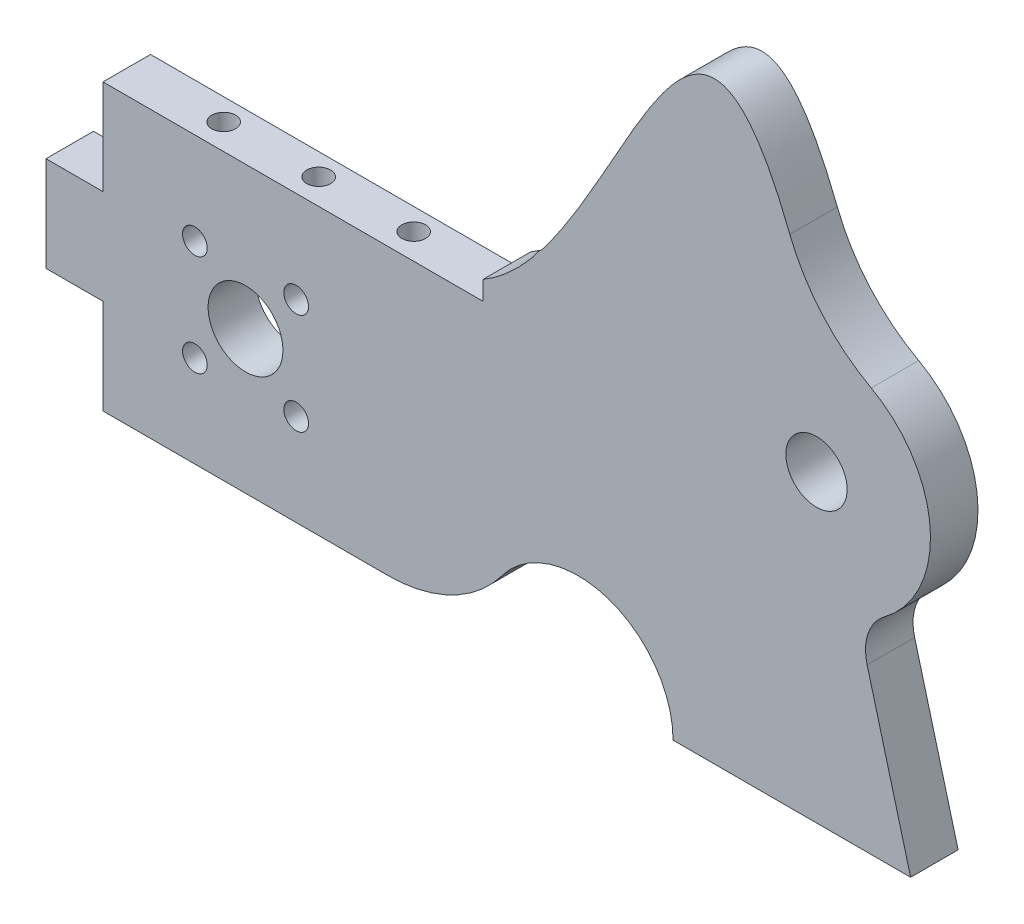
SolidWorks part; units mm, degrees
ref_plane "Front Plane" through (0, 0, 0) normal (0, 0, 1) x (1, 0, 0)
ref_plane "Top Plane" through (0, 0, 0) normal (0, 1, 0) x (1, 0, 0)
ref_plane "Right Plane" through (0, 0, 0) normal (1, 0, 0) x (0, 0, -1)
sketch "Sketch1" plane through (0, 0, 0) normal (0, 0, 1) x (1, 0, 0)
  line L0 (0, 0) -> (107.95, 0)
  line L3 (0, 38.1) -> (0, 25.4)
  line L4 (95.3675, 55.88) -> (0, 38.1)
  line L5 (0, 19.05) -> (100.2273, 19.05) construction
  line L6 (19.05, 19.05) -> (19.05, 28.62) construction
  line L7 (19.05, 19.05) -> (25.817, 25.817) construction
  line L8 (107.95, 0) -> (100.9363, 26.1756)
  line L10 (0, 12.7) -> (0, 0)
  line L11 (0, 25.4) -> (-7.62, 25.4)
  line L13 (0, 12.7) -> (-7.62, 12.7)
  line L14 (-7.62, 25.4) -> (-7.62, 12.7)
  line L15 (100.9363, 26.1756) -> (100.8688, 26.4276)
  arc A0 (100.8688, 26.4276) -> (95.3675, 55.88) centre (95.3675, 40.64) ccw
  circle A1 centre (95.3675, 40.64) radius 4.0957
  circle A2 centre (19.05, 19.05) radius 9.57 construction
  circle A3 centre (25.817, 25.817) radius 1.651
  circle A4 centre (25.817, 12.283) radius 1.651
  circle A5 centre (12.283, 12.283) radius 1.651
  circle A6 centre (12.283, 25.817) radius 1.651
  point P26 (19.05, 19.05)
  dimension "D1" = 8.1915
  dimension "D5" = 15.24
  dimension "D4" = 19.14
  dimension "D7" = 3.302
  dimension "D11" = 97.0107
  dimension "D2" = 38.1
  dimension "D3" = 40.64
  dimension "D6" = 107.95
  dimension "D8" = 45
  dimension "D9" = 4
  dimension "D10" = 19.05
  dimension "D12" = 75
  dimension "D14" = 12.7
  dimension "D15" = 12.7
  dimension "D16" = 7.62
extrude "Boss-Extrude1" add sketch "Sketch1" along normal blind 6.35
sketch "Sketch2" plane through (0, 0, 6.35) normal (0, 0, 1) x (1, 0, 0)
  circle A0 centre (95.3675, 40.64) radius 38.1 construction
sketch "Sketch3" plane through (0, 0, 0) normal (-1, 0, 0) x (0, 0, 1)
  line L0 (0, 38.1) -> (6.35, 25.4) construction
  line L1 (6.35, 12.7) -> (0, 0) construction
  circle A0 centre (3.175, 31.75) radius 1.5875
  circle A1 centre (3.175, 6.35) radius 1.5875
  dimension "D1" = 3.175
  dimension "D2" = 3.175
extrude "Cut-Extrude1" cut sketch "Sketch3" against normal blind 6.35
sketch "Sketch6" plane through (0, 0, 6.35) normal (0, 0, 1) x (1, 0, 0)
  line L0 (0, 0) -> (107.95, 0) construction
  line L1 (50.8, 0) -> (76.2, 0)
  arc A0 (76.2, 0) -> (50.8, 0) centre (63.5, 0) ccw
  dimension "D1" = 25.4
  dimension "D2" = 31.75
extrude "Cut-Extrude2" cut sketch "Sketch6" against normal blind 6.35
sketch "Sketch7" plane through (0, 0, 6.35) normal (0, 0, 1) x (1, 0, 0)
  line L0 (12.283, 25.817) -> (25.817, 12.283) construction
  line L1 (12.283, 12.283) -> (25.817, 25.817) construction
  circle A0 centre (19.05, 19.05) radius 5
  dimension "D1" = 10
extrude "Cut-Extrude3" cut sketch "Sketch7" against normal through all
fillet "Fillet1" radius 6.35 1 edges at (100.8688, 26.4276, 3.175)
sketch "Sketch8" plane through (0, 0, 6.35) normal (0, 0, 1) x (1, 0, 0)
  line L1 (0, 38.1) -> (50.8, 38.1)
  line L2 (0, 38.1) -> (0, 50.8)
  line L3 (0, 50.8) -> (50.8, 50.8)
  line L4 (50.8, 38.1) -> (50.8, 50.8)
  dimension "D1" = 50.8
  dimension "D2" = 12.7
extrude "Cut-Extrude4" cut sketch "Sketch8" against normal blind 50.8
sketch "Sketch9" plane through (0, 0, 6.35) normal (0, 0, 1) x (1, 0, 0)
  line L3 (50.8, 40.64) -> (57.15, 40.64)
  line L5 (57.15, 40.64) -> (50.8, 40.64)
  line L6 (57.15, 40.64) -> (57.15, 50.8)
  line L7 (57.15, 50.8) -> (50.8, 50.8)
  line L8 (50.8, 40.64) -> (50.8, 50.8)
  line L9 (0, 38.1) -> (50.8, 38.1) construction
  line M8 (50.8, 47.571) -> (50.8, 38.1)
  line M21 (95.3675, 55.88) -> (50.8, 47.571)
  dimension "D1" = 10.16
  dimension "D2" = 2.54
  dimension "D3" = 6.35
extrude "Cut-Extrude5" cut sketch "Sketch9" against normal blind 19.304 contours L3 L6 M21 M8 region at (54.0583, 44.4092, 6.35)
fillet "Fillet6" radius 6.35 1 edges at (57.15, 40.64, 3.175)
fillet "Fillet7" radius 6.35 1 edges at (57.15, 48.7549, 3.175)
fillet "Fillet8" radius 19.05 1 edges at (50.8, 0, 3.175)
sketch "Sketch10" plane through (0, 0, 0) normal (0, -1, 0) x (1, 0, 0)
  line L0 (76.2, 6.35) -> (107.95, 6.35) construction
  line L1 (0, 6.35) -> (0, 0) construction
  line L2 (0, 6.35) -> (38.1, 6.35) construction
  line L3 (107.95, 6.35) -> (107.95, 0) construction
  line L4 (76.2, 0) -> (76.2, 6.35) construction
  circle A0 centre (97.79, 3.175) radius 1.5875
  circle A1 centre (86.36, 3.175) radius 1.5875
  circle A2 centre (31.75, 3.175) radius 1.5875
  circle A3 centre (12.7, 3.175) radius 1.5875
  dimension "D1" = 3.175
  dimension "D2" = 3.175
  dimension "D3" = 3.175
  dimension "D4" = 3.175
  dimension "D5" = 12.7
  dimension "D6" = 19.05
  dimension "D7" = 10.16
  dimension "D8" = 10.16
  dimension "D9" = 11.43
  dimension "D10" = 3.175
  dimension "D11" = 3.175
extrude "Cut-Extrude6" cut sketch "Sketch10" against normal blind 6.35
sketch "Sketch11" plane through (0, 38.1, 0) normal (0, 1, 0) x (1, 0, 0)
  line L0 (0, -6.35) -> (0, 0) construction
  line L1 (50.8, 0) -> (50.8, -6.35) construction
  line L2 (0, -6.35) -> (50.8, -6.35) construction
  circle A0 centre (12.7, -2.9224) radius 1.5875
  circle A1 centre (25.4, -2.9224) radius 1.5875
  circle A2 centre (38.1, -2.9224) radius 1.5875
  dimension "D1" = 3.175
  dimension "D2" = 3.175
  dimension "D3" = 3.175
  dimension "D4" = 12.7
  dimension "D5" = 12.7
  dimension "D6" = 12.7
  dimension "D7" = 12.7
  dimension "D8" = 3.4276
extrude "Cut-Extrude7" cut sketch "Sketch11" against normal blind 6.35
sketch "Sketch12" plane through (0, 0, 6.35) normal (0, 0, 1) x (1, 0, 0)
  line L0 (107.95, 0) -> (146.812, 0) construction
  line L1 (8.0257, 45.4128) -> (80.6683, 75.7903) construction
  line L2 (95.3675, 40.64) -> (80.6683, 75.7903) construction
  line L3 (80.6683, 75.7903) -> (79.4434, 78.7195) construction
  line L4 (50.8, 40.64) -> (85.0271, 40.64)
  line L5 (85.0271, 40.64) -> (95.3675, 55.88)
  arc A0 (61.8128, 49.6242) -> (56.8883, 45.1859) centre (62.9766, 43.3817) ccw construction
  circle A1 centre (19.05, 19.05) radius 28.575 construction
  circle A2 centre (95.3675, 40.64) radius 38.1 construction
  circle A3 centre (80.6683, 75.7903) radius 3.175 construction
  spline S0 degree 3 poles (50.8, 40.64) (70.7778, 52.1788) (78.5943, 111.5434) (95.3675, 55.88) knots 0 0 0 0 1 1 1 1
  dimension "D2" = 6.35
  dimension "D1" = 38.862
extrude "Boss-Extrude2" add sketch "Sketch12" against normal blind 6.35
fillet "Fillet9" radius 24.13 1 edges at (95.3675, 55.88, 3.175)
